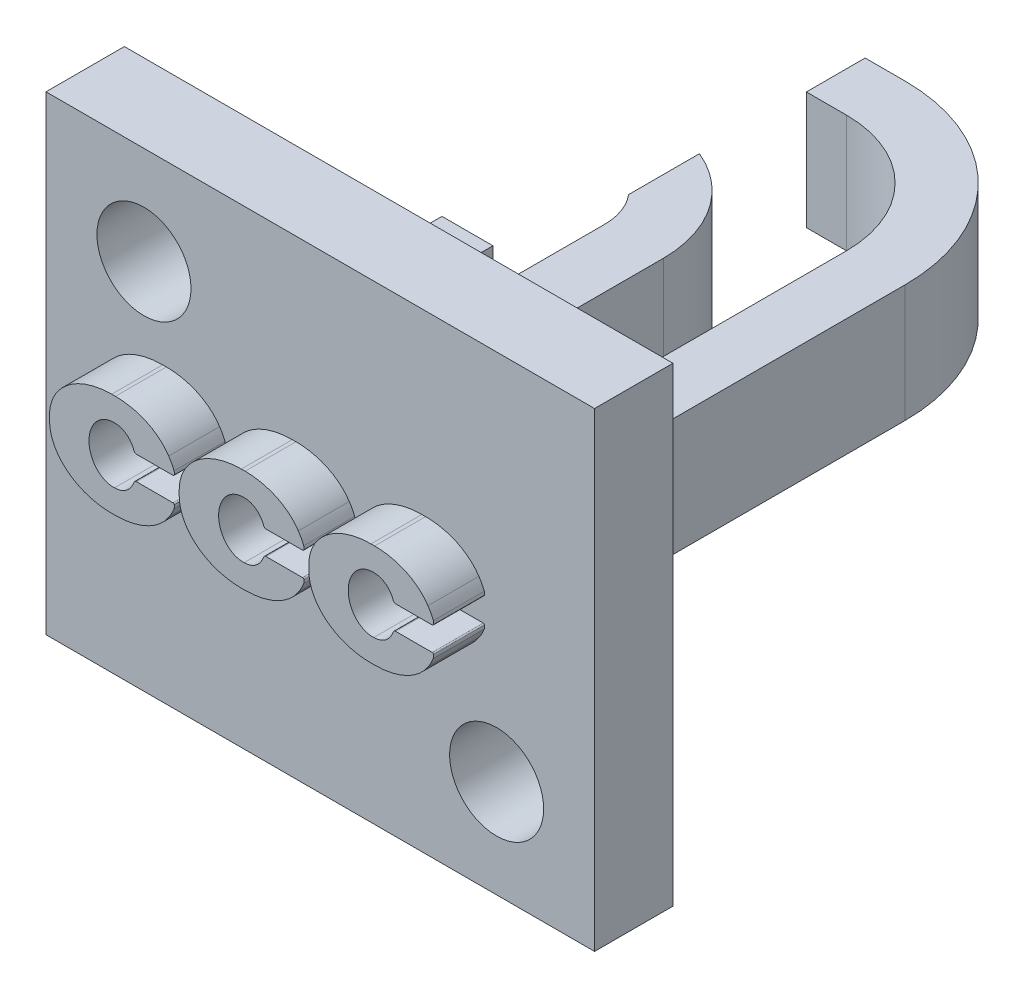
SolidWorks part; units mm, degrees
ref_plane "Front Plane" through (0, 0, 0) normal (0, 0, 1) x (1, 0, 0)
ref_plane "Top Plane" through (0, 0, 0) normal (0, 1, 0) x (1, 0, 0)
ref_plane "Right Plane" through (0, 0, 0) normal (1, 0, 0) x (0, 0, -1)
sketch "Sketch1" plane through (0, 0, 0) normal (0, 0, 1) x (1, 0, 0)
  line L1 (-7.5, 6) -> (7.5, 6)
  line L2 (-7.5, 6) -> (-7.5, -6)
  line L3 (-7.5, -6) -> (7.5, -6)
  line L4 (7.5, 6) -> (7.5, -6)
  line L5 (-7.5, 6) -> (7.5, -6) construction
  line L6 (-7.5, -6) -> (7.5, 6) construction
  point P0 (0, 0)
  dimension "D1" = 15
  dimension "D2" = 12
extrude "Boss-Extrude1" add sketch "Sketch1" along normal blind 2
sketch "Sketch2" plane through (0, 0, 2) normal (0, 0, 1) x (1, 0, 0)
  line L0 (-0.5835, 0.4438) -> (0.3524, 0.4438)
  line L1 (-1.1209, 1.4546) -> (-1.2145, 1.4546)
  line L2 (-2.8001, 0.2034) -> (-2.8001, 0.0733)
  line L3 (-1.2145, -1.1779) -> (-1.1209, -1.1779)
  line L4 (0.3478, -0.1633) -> (-0.5835, -0.1633)
  line L5 (-3.8918, 0.4438) -> (-2.956, 0.4438)
  line L6 (-4.4292, 1.4546) -> (-4.5228, 1.4546)
  line L7 (-6.1084, 0.2034) -> (-6.1084, 0.0733)
  line L8 (-4.5228, -1.1779) -> (-4.4292, -1.1779)
  line L9 (-2.9605, -0.1633) -> (-3.8918, -0.1633)
  line L10 (2.7248, 0.4438) -> (3.6607, 0.4438)
  line L11 (2.1874, 1.4546) -> (2.0938, 1.4546)
  line L12 (0.5082, 0.2034) -> (0.5082, 0.0733)
  line L13 (2.0938, -1.1779) -> (2.1874, -1.1779)
  line L14 (3.6561, -0.1633) -> (2.7248, -0.1633)
  arc A0 (-0.6452, 0.4874) -> (-0.5835, 0.4438) centre (-0.5835, 0.5092) ccw
  arc A1 (0.3524, 0.4438) -> (0.3816, 0.4686) centre (0.3479, 0.4787) ccw
  arc A2 (0.3816, 0.4686) -> (0.3774, 0.5561) centre (0.201, 0.5038) ccw
  arc A3 (0.3774, 0.5561) -> (0.2402, 0.8134) centre (-0.7046, 0.1445) ccw
  arc A4 (0.2402, -0.5368) -> (0.3727, -0.2904) centre (-0.6952, 0.1249) ccw
  arc A5 (0.3727, -0.2904) -> (0.3825, -0.1925) centre (0.2012, -0.2237) ccw
  arc A6 (0.3825, -0.1925) -> (0.3478, -0.1633) centre (0.3478, -0.1984) ccw
  arc A7 (-0.5835, -0.1633) -> (-0.6452, -0.2069) centre (-0.5835, -0.2287) ccw
  arc A8 (-3.9535, 0.4874) -> (-3.8918, 0.4438) centre (-3.8918, 0.5092) ccw
  arc A9 (-2.956, 0.4438) -> (-2.9267, 0.4686) centre (-2.9604, 0.4787) ccw
  arc A10 (-2.9267, 0.4686) -> (-2.9309, 0.5561) centre (-3.1073, 0.5038) ccw
  arc A11 (-2.9309, 0.5561) -> (-3.0681, 0.8134) centre (-4.0129, 0.1445) ccw
  arc A12 (-3.0681, -0.5368) -> (-2.9356, -0.2904) centre (-4.0035, 0.1249) ccw
  arc A13 (-2.9356, -0.2904) -> (-2.9258, -0.1925) centre (-3.1071, -0.2237) ccw
  arc A14 (-2.9258, -0.1925) -> (-2.9605, -0.1633) centre (-2.9605, -0.1984) ccw
  arc A15 (-3.8918, -0.1633) -> (-3.9535, -0.2069) centre (-3.8918, -0.2287) ccw
  arc A16 (2.6631, 0.4874) -> (2.7248, 0.4438) centre (2.7248, 0.5092) ccw
  arc A17 (3.6607, 0.4438) -> (3.6899, 0.4686) centre (3.6562, 0.4787) ccw
  arc A18 (3.6899, 0.4686) -> (3.6857, 0.5561) centre (3.5093, 0.5038) ccw
  arc A19 (3.6857, 0.5561) -> (3.5485, 0.8134) centre (2.6037, 0.1445) ccw
  arc A20 (3.5485, -0.5368) -> (3.681, -0.2904) centre (2.6131, 0.1249) ccw
  arc A21 (3.681, -0.2904) -> (3.6908, -0.1925) centre (3.5095, -0.2237) ccw
  arc A22 (3.6908, -0.1925) -> (3.6561, -0.1633) centre (3.6561, -0.1984) ccw
  arc A23 (2.7248, -0.1633) -> (2.6631, -0.2069) centre (2.7248, -0.2287) ccw
  ellipse E0 centre (-1.1734, 0.1385) end of major axis (-1.177, 0.8556) minor radius 0.6209 (-1.2015, 0.8549) -> (-1.1417, -0.5777) ccw
  ellipse E1 centre (-1.2295, 0.1385) end of major axis (-1.5121, -0.5431) minor radius 0.6039 (-0.6452, 0.4874) -> (-1.2015, 0.8549) ccw
  ellipse E2 centre (-1.2429, 0.1529) end of major axis (-2.8857, -0.0922) minor radius 1.2925 (0.2402, 0.8134) -> (-1.1209, 1.4546) ccw
  ellipse E3 centre (-1.1521, 0.1542) end of major axis (0.4928, 0.0248) minor radius 1.2979 (-1.2145, 1.4546) -> (-2.8001, 0.2034) ccw
  ellipse E4 centre (-1.1521, 0.1225) end of major axis (0.4928, 0.2518) minor radius 1.2979 (-2.8001, 0.0733) -> (-1.2145, -1.1779) ccw
  ellipse E5 centre (-1.2429, 0.1238) end of major axis (-2.8857, 0.3689) minor radius 1.2925 (-1.1209, -1.1779) -> (0.2402, -0.5368) ccw
  ellipse E6 centre (-1.2295, 0.1421) end of major axis (-0.9469, -0.5396) minor radius 0.6039 (-1.1417, -0.5777) -> (-0.6452, -0.2069) ccw
  ellipse E7 centre (-4.5378, 0.1385) end of major axis (-4.8204, -0.5431) minor radius 0.6039 (-3.9535, 0.4874) -> (-4.5098, 0.8549) ccw
  ellipse E8 centre (-4.5512, 0.1529) end of major axis (-6.194, -0.0922) minor radius 1.2925 (-3.0681, 0.8134) -> (-4.4292, 1.4546) ccw
  ellipse E9 centre (-4.4604, 0.1542) end of major axis (-6.1053, 0.2835) minor radius 1.2979 (-4.5228, 1.4546) -> (-6.1084, 0.2034) ccw
  ellipse E10 centre (-4.4604, 0.1225) end of major axis (-6.1053, -0.0069) minor radius 1.2979 (-6.1084, 0.0733) -> (-4.5228, -1.1779) ccw
  ellipse E11 centre (-4.5512, 0.1238) end of major axis (-6.194, 0.3689) minor radius 1.2925 (-4.4292, -1.1779) -> (-3.0681, -0.5368) ccw
  ellipse E12 centre (-4.5378, 0.1421) end of major axis (-4.2552, -0.5396) minor radius 0.6039 (-4.45, -0.5777) -> (-3.9535, -0.2069) ccw
  ellipse E13 centre (-4.4817, 0.1385) end of major axis (-4.4853, 0.8556) minor radius 0.6209 (-4.5098, 0.8549) -> (-4.45, -0.5777) ccw
  ellipse E14 centre (2.1349, 0.1385) end of major axis (2.1385, -0.5786) minor radius 0.6209 (2.1069, 0.8549) -> (2.1666, -0.5777) ccw
  ellipse E15 centre (2.0788, 0.1385) end of major axis (2.3614, 0.8201) minor radius 0.6039 (2.6631, 0.4874) -> (2.1069, 0.8549) ccw
  ellipse E16 centre (2.0654, 0.1529) end of major axis (3.7082, 0.3981) minor radius 1.2925 (3.5485, 0.8134) -> (2.1874, 1.4546) ccw
  ellipse E17 centre (2.1562, 0.1542) end of major axis (0.5113, 0.2835) minor radius 1.2979 (2.0938, 1.4546) -> (0.5082, 0.2034) ccw
  ellipse E18 centre (2.1562, 0.1225) end of major axis (3.8011, 0.2518) minor radius 1.2979 (0.5082, 0.0733) -> (2.0938, -1.1779) ccw
  ellipse E19 centre (2.0654, 0.1238) end of major axis (0.4226, 0.3689) minor radius 1.2925 (2.1874, -1.1779) -> (3.5485, -0.5368) ccw
  ellipse E20 centre (2.0788, 0.1421) end of major axis (2.3614, -0.5396) minor radius 0.6039 (2.1666, -0.5777) -> (2.6631, -0.2069) ccw
extrude "Boss-Extrude2" add sketch "Sketch2" along normal blind 2
sketch "Sketch3" plane through (0, 0, 0) normal (0, 1, 0) x (1, 0, 0)
  line L0 (7.5, 0) -> (-7.5, 0) construction
  line L1 (1.7287, 0) -> (3.2287, 0)
  line L2 (1.7287, 0) -> (1.7287, 12.2)
  line L3 (-3.644, -2) -> (-3.644, 5.3789) construction
  line L4 (3.2287, 0) -> (3.2287, 13.7)
  line L5 (-4.394, 0) -> (-2.894, 0)
  line L6 (-4.394, 0) -> (-4.394, 4.8)
  line L7 (-1.1926, -2) -> (-1.1926, 4.6797) construction
  line L8 (-2.894, 0) -> (-2.894, 4.8)
  line L9 (-2.894, 4.8) -> (-4.394, 4.8)
  line L10 (-1.9426, 0) -> (-0.4426, 0)
  line L13 (-1.9426, 0) -> (-1.9426, 8.2)
  line L14 (2.4787, -2) -> (2.4787, 2.787) construction
  line L15 (-0.4426, 0) -> (-0.4426, 9.7)
  line L16 (-0.4426, 9.7) -> (-3.4426, 9.7)
  line L17 (-3.4426, 13.7) -> (3.2287, 13.7)
  line L18 (-1.9426, 8.2) -> (-3.4426, 8.2)
  line L19 (-3.4426, 9.7) -> (-3.4426, 8.2)
  line L20 (-3.4426, 13.7) -> (-3.4426, 12.2)
  line L21 (-3.4426, 12.2) -> (1.7287, 12.2)
  dimension "D1" = 1.5
  dimension "D2" = 4.8
  dimension "D3" = 1.5
  dimension "D4" = 1.5
  dimension "D5" = 8.2
  dimension "D6" = 1.5
  dimension "D7" = 2.5
  dimension "D8" = 1.5
  dimension "D9" = 1.5
  dimension "D10" = 3.644
  dimension "D11" = 1.1926
  dimension "D12" = 2.4787
extrude "Boss-Extrude3" add sketch "Sketch3" along normal mid plane 3
fillet "Fillet3" radius 1.5 1 edges at (-1.9426, 0, -8.2)
fillet "Fillet4" radius 3 1 edges at (-0.4426, 0, -9.7)
fillet "Fillet5" radius 3 1 edges at (1.7287, 0, -12.2)
fillet "Fillet6" radius 4.5 1 edges at (3.2287, 0, -13.7)
sketch "Sketch4" plane through (7.5, 0, 0) normal (1, 0, 0) x (0, 0, -1)
  line L4 (0, -6) -> (0, 6)
  line L5 (0, 6) -> (-2, 6)
  line L6 (-2, 6) -> (-2, -6)
  line L7 (-2, -6) -> (0, -6)
  line L8 (0, -6) -> (0, 6)
  line L9 (0, 6) -> (-2, 6)
  line L10 (-2, 6) -> (-2, -6)
  line L11 (-2, -6) -> (0, -6)
  dimension "D1" = 0
extrude "Cut-Extrude1" cut sketch "Sketch4" against normal blind 1
sketch "Sketch5" plane through (0, 0, 0) normal (0, 0, -1) x (-1, 0, 0)
  line L0 (-6.5, -6) -> (-6.5, 6) construction
  line L1 (7.5, -6) -> (-6.5, -6) construction
  line L2 (7.5, 6) -> (7.5, -6) construction
  line L3 (-6.5, 6) -> (7.5, 6) construction
  circle A0 centre (-4, -3.5) radius 1.2
  circle A1 centre (5, 3.5) radius 1.2
  dimension "D1" = 2.4
  dimension "D2" = 2.5
  dimension "D3" = 2.5
  dimension "D4" = 2.5
  dimension "D5" = 2.5
extrude "Cut-Extrude2" cut sketch "Sketch5" against normal through all
sketch "Sketch6" plane through (0, 0, 4) normal (0, 0, 1) x (1, 0, 0)
  line L0 (2.7248, 0.4438) -> (3.6607, 0.4438) construction
  line L1 (2.1874, 1.4546) -> (2.0938, 1.4546) construction
  line L2 (0.5082, 0.2034) -> (0.5082, 0.0733) construction
  line L3 (2.0938, -1.1779) -> (2.1874, -1.1779) construction
  line L4 (3.6561, -0.1633) -> (2.7248, -0.1633) construction
  line L5 (-0.5835, 0.4438) -> (0.3524, 0.4438) construction
  line L6 (-1.1209, 1.4546) -> (-1.2145, 1.4546) construction
  line L7 (-2.8001, 0.2034) -> (-2.8001, 0.0733) construction
  line L8 (-1.2145, -1.1779) -> (-1.1209, -1.1779) construction
  line L9 (0.3478, -0.1633) -> (-0.5835, -0.1633) construction
  line L10 (-3.8918, 0.4438) -> (-2.956, 0.4438) construction
  line L11 (-4.4292, 1.4546) -> (-4.5228, 1.4546) construction
  line L12 (-6.1084, 0.2034) -> (-6.1084, 0.0733) construction
  line L13 (-4.5228, -1.1779) -> (-4.4292, -1.1779) construction
  line L14 (-2.9605, -0.1633) -> (-3.8918, -0.1633) construction
  line L15 (2.7248, 0.4438) -> (3.6607, 0.4438)
  line L16 (2.1874, 1.4546) -> (2.0938, 1.4546)
  line L17 (0.5082, 0.2034) -> (0.5082, 0.0733)
  line L18 (2.0938, -1.1779) -> (2.1874, -1.1779)
  line L19 (3.6561, -0.1633) -> (2.7248, -0.1633)
  line L20 (-0.5835, 0.4438) -> (0.3524, 0.4438)
  line L21 (-1.1209, 1.4546) -> (-1.2145, 1.4546)
  line L22 (-2.8001, 0.2034) -> (-2.8001, 0.0733)
  line L23 (-1.2145, -1.1779) -> (-1.1209, -1.1779)
  line L24 (0.3478, -0.1633) -> (-0.5835, -0.1633)
  line L25 (-3.8918, 0.4438) -> (-2.956, 0.4438)
  line L26 (-4.4292, 1.4546) -> (-4.5228, 1.4546)
  line L27 (-6.1084, 0.2034) -> (-6.1084, 0.0733)
  line L28 (-4.5228, -1.1779) -> (-4.4292, -1.1779)
  line L29 (-2.9605, -0.1633) -> (-3.8918, -0.1633)
  arc A0 (2.6631, 0.4874) -> (2.7248, 0.4438) centre (2.7248, 0.5092) ccw construction
  arc A1 (3.6607, 0.4438) -> (3.6899, 0.4686) centre (3.6562, 0.4787) ccw construction
  arc A2 (3.6899, 0.4686) -> (3.6857, 0.5561) centre (3.5093, 0.5038) ccw construction
  arc A3 (3.6857, 0.5561) -> (3.5485, 0.8134) centre (2.6037, 0.1445) ccw construction
  arc A4 (3.5485, -0.5368) -> (3.681, -0.2904) centre (2.6131, 0.1249) ccw construction
  arc A5 (3.681, -0.2904) -> (3.6908, -0.1925) centre (3.5095, -0.2237) ccw construction
  arc A6 (3.6908, -0.1925) -> (3.6561, -0.1633) centre (3.6561, -0.1984) ccw construction
  arc A7 (2.7248, -0.1633) -> (2.6631, -0.2069) centre (2.7248, -0.2287) ccw construction
  arc A8 (-0.6452, 0.4874) -> (-0.5835, 0.4438) centre (-0.5835, 0.5092) ccw construction
  arc A9 (0.3524, 0.4438) -> (0.3816, 0.4686) centre (0.3479, 0.4787) ccw construction
  arc A10 (0.3816, 0.4686) -> (0.3774, 0.5561) centre (0.201, 0.5038) ccw construction
  arc A11 (0.3774, 0.5561) -> (0.2402, 0.8134) centre (-0.7046, 0.1445) ccw construction
  arc A12 (0.2402, -0.5368) -> (0.3727, -0.2904) centre (-0.6952, 0.1249) ccw construction
  arc A13 (0.3727, -0.2904) -> (0.3825, -0.1925) centre (0.2012, -0.2237) ccw construction
  arc A14 (0.3825, -0.1925) -> (0.3478, -0.1633) centre (0.3478, -0.1984) ccw construction
  arc A15 (-0.5835, -0.1633) -> (-0.6452, -0.2069) centre (-0.5835, -0.2287) ccw construction
  arc A16 (-3.9535, 0.4874) -> (-3.8918, 0.4438) centre (-3.8918, 0.5092) ccw construction
  arc A17 (-2.956, 0.4438) -> (-2.9267, 0.4686) centre (-2.9604, 0.4787) ccw construction
  arc A18 (-2.9267, 0.4686) -> (-2.9309, 0.5561) centre (-3.1073, 0.5038) ccw construction
  arc A19 (-2.9309, 0.5561) -> (-3.0681, 0.8134) centre (-4.0129, 0.1445) ccw construction
  arc A20 (-3.0681, -0.5368) -> (-2.9356, -0.2904) centre (-4.0035, 0.1249) ccw construction
  arc A21 (-2.9356, -0.2904) -> (-2.9258, -0.1925) centre (-3.1071, -0.2237) ccw construction
  arc A22 (-2.9258, -0.1925) -> (-2.9605, -0.1633) centre (-2.9605, -0.1984) ccw construction
  arc A23 (-3.8918, -0.1633) -> (-3.9535, -0.2069) centre (-3.8918, -0.2287) ccw construction
  arc A24 (2.6631, 0.4874) -> (2.7248, 0.4438) centre (2.7248, 0.5092) ccw
  arc A25 (3.6607, 0.4438) -> (3.6899, 0.4686) centre (3.6562, 0.4787) ccw
  arc A26 (3.6899, 0.4686) -> (3.6857, 0.5561) centre (3.5093, 0.5038) ccw
  arc A27 (3.6857, 0.5561) -> (3.5485, 0.8134) centre (2.6037, 0.1445) ccw
  arc A28 (3.5485, -0.5368) -> (3.681, -0.2904) centre (2.6131, 0.1249) ccw
  arc A29 (3.681, -0.2904) -> (3.6908, -0.1925) centre (3.5095, -0.2237) ccw
  arc A30 (3.6908, -0.1925) -> (3.6561, -0.1633) centre (3.6561, -0.1984) ccw
  arc A31 (2.7248, -0.1633) -> (2.6631, -0.2069) centre (2.7248, -0.2287) ccw
  arc A32 (-0.6452, 0.4874) -> (-0.5835, 0.4438) centre (-0.5835, 0.5092) ccw
  arc A33 (0.3524, 0.4438) -> (0.3816, 0.4686) centre (0.3479, 0.4787) ccw
  arc A34 (0.3816, 0.4686) -> (0.3774, 0.5561) centre (0.201, 0.5038) ccw
  arc A35 (0.3774, 0.5561) -> (0.2402, 0.8134) centre (-0.7046, 0.1445) ccw
  arc A36 (0.2402, -0.5368) -> (0.3727, -0.2904) centre (-0.6952, 0.1249) ccw
  arc A37 (0.3727, -0.2904) -> (0.3825, -0.1925) centre (0.2012, -0.2237) ccw
  arc A38 (0.3825, -0.1925) -> (0.3478, -0.1633) centre (0.3478, -0.1984) ccw
  arc A39 (-0.5835, -0.1633) -> (-0.6452, -0.2069) centre (-0.5835, -0.2287) ccw
  arc A40 (-3.9535, 0.4874) -> (-3.8918, 0.4438) centre (-3.8918, 0.5092) ccw
  arc A41 (-2.956, 0.4438) -> (-2.9267, 0.4686) centre (-2.9604, 0.4787) ccw
  arc A42 (-2.9267, 0.4686) -> (-2.9309, 0.5561) centre (-3.1073, 0.5038) ccw
  arc A43 (-2.9309, 0.5561) -> (-3.0681, 0.8134) centre (-4.0129, 0.1445) ccw
  arc A44 (-3.0681, -0.5368) -> (-2.9356, -0.2904) centre (-4.0035, 0.1249) ccw
  arc A45 (-2.9356, -0.2904) -> (-2.9258, -0.1925) centre (-3.1071, -0.2237) ccw
  arc A46 (-2.9258, -0.1925) -> (-2.9605, -0.1633) centre (-2.9605, -0.1984) ccw
  arc A47 (-3.8918, -0.1633) -> (-3.9535, -0.2069) centre (-3.8918, -0.2287) ccw
  ellipse E0 centre (2.0788, 0.1385) end of major axis (1.7962, -0.5431) minor radius 0.6039 (2.6631, 0.4874) -> (2.1069, 0.8549) ccw construction
  ellipse E1 centre (2.0654, 0.1529) end of major axis (0.4226, -0.0922) minor radius 1.2925 (3.5485, 0.8134) -> (2.1874, 1.4546) ccw construction
  ellipse E2 centre (2.1562, 0.1542) end of major axis (0.5113, 0.2835) minor radius 1.2979 (2.0938, 1.4546) -> (0.5082, 0.2034) ccw construction
  ellipse E3 centre (2.1562, 0.1225) end of major axis (3.8011, 0.2518) minor radius 1.2979 (0.5082, 0.0733) -> (2.0938, -1.1779) ccw construction
  ellipse E4 centre (2.0654, 0.1238) end of major axis (0.4226, 0.3689) minor radius 1.2925 (2.1874, -1.1779) -> (3.5485, -0.5368) ccw construction
  ellipse E5 centre (2.0788, 0.1421) end of major axis (2.3614, -0.5396) minor radius 0.6039 (2.1666, -0.5777) -> (2.6631, -0.2069) ccw construction
  ellipse E6 centre (2.1349, 0.1385) end of major axis (2.1385, -0.5786) minor radius 0.6209 (2.1069, 0.8549) -> (2.1666, -0.5777) ccw construction
  ellipse E7 centre (-1.2295, 0.1385) end of major axis (-1.5121, -0.5431) minor radius 0.6039 (-0.6452, 0.4874) -> (-1.2015, 0.8549) ccw construction
  ellipse E8 centre (-1.2429, 0.1529) end of major axis (0.3999, 0.3981) minor radius 1.2925 (0.2402, 0.8134) -> (-1.1209, 1.4546) ccw construction
  ellipse E9 centre (-1.1521, 0.1542) end of major axis (-2.797, 0.2835) minor radius 1.2979 (-1.2145, 1.4546) -> (-2.8001, 0.2034) ccw construction
  ellipse E10 centre (-1.1521, 0.1225) end of major axis (0.4928, 0.2518) minor radius 1.2979 (-2.8001, 0.0733) -> (-1.2145, -1.1779) ccw construction
  ellipse E11 centre (-1.2429, 0.1238) end of major axis (0.3999, -0.1214) minor radius 1.2925 (-1.1209, -1.1779) -> (0.2402, -0.5368) ccw construction
  ellipse E12 centre (-1.2295, 0.1421) end of major axis (-0.9469, -0.5396) minor radius 0.6039 (-1.1417, -0.5777) -> (-0.6452, -0.2069) ccw construction
  ellipse E13 centre (-1.1734, 0.1385) end of major axis (-1.1698, -0.5786) minor radius 0.6209 (-1.2015, 0.8549) -> (-1.1417, -0.5777) ccw construction
  ellipse E14 centre (-4.5378, 0.1385) end of major axis (-4.8204, -0.5431) minor radius 0.6039 (-3.9535, 0.4874) -> (-4.5098, 0.8549) ccw construction
  ellipse E15 centre (-4.5512, 0.1529) end of major axis (-2.9084, 0.3981) minor radius 1.2925 (-3.0681, 0.8134) -> (-4.4292, 1.4546) ccw construction
  ellipse E16 centre (-4.4604, 0.1542) end of major axis (-6.1053, 0.2835) minor radius 1.2979 (-4.5228, 1.4546) -> (-6.1084, 0.2034) ccw construction
  ellipse E17 centre (-4.4604, 0.1225) end of major axis (-2.8155, 0.2518) minor radius 1.2979 (-6.1084, 0.0733) -> (-4.5228, -1.1779) ccw construction
  ellipse E18 centre (-4.5512, 0.1238) end of major axis (-6.194, 0.3689) minor radius 1.2925 (-4.4292, -1.1779) -> (-3.0681, -0.5368) ccw construction
  ellipse E19 centre (-4.5378, 0.1421) end of major axis (-4.2552, -0.5396) minor radius 0.6039 (-4.45, -0.5777) -> (-3.9535, -0.2069) ccw construction
  ellipse E20 centre (-4.4817, 0.1385) end of major axis (-4.4781, -0.5786) minor radius 0.6209 (-4.5098, 0.8549) -> (-4.45, -0.5777) ccw construction
  ellipse E21 centre (2.0788, 0.1385) end of major axis (1.7962, -0.5431) minor radius 0.6039 (2.6631, 0.4874) -> (2.1069, 0.8549) ccw
  ellipse E22 centre (2.0654, 0.1529) end of major axis (3.7082, 0.3981) minor radius 1.2925 (3.5485, 0.8134) -> (2.1874, 1.4546) ccw
  ellipse E23 centre (2.1562, 0.1542) end of major axis (0.5113, 0.2835) minor radius 1.2979 (2.0938, 1.4546) -> (0.5082, 0.2034) ccw
  ellipse E24 centre (2.1562, 0.1225) end of major axis (3.8011, 0.2518) minor radius 1.2979 (0.5082, 0.0733) -> (2.0938, -1.1779) ccw
  ellipse E25 centre (2.0654, 0.1238) end of major axis (0.4226, 0.3689) minor radius 1.2925 (2.1874, -1.1779) -> (3.5485, -0.5368) ccw
  ellipse E26 centre (2.0788, 0.1421) end of major axis (2.3614, -0.5396) minor radius 0.6039 (2.1666, -0.5777) -> (2.6631, -0.2069) ccw
  ellipse E27 centre (2.1349, 0.1385) end of major axis (2.1385, -0.5786) minor radius 0.6209 (2.1069, 0.8549) -> (2.1666, -0.5777) ccw
  ellipse E28 centre (-1.2295, 0.1385) end of major axis (-1.5121, -0.5431) minor radius 0.6039 (-0.6452, 0.4874) -> (-1.2015, 0.8549) ccw
  ellipse E29 centre (-1.2429, 0.1529) end of major axis (0.3999, 0.3981) minor radius 1.2925 (0.2402, 0.8134) -> (-1.1209, 1.4546) ccw
  ellipse E30 centre (-1.1521, 0.1542) end of major axis (-2.797, 0.2835) minor radius 1.2979 (-1.2145, 1.4546) -> (-2.8001, 0.2034) ccw
  ellipse E31 centre (-1.1521, 0.1225) end of major axis (0.4928, 0.2518) minor radius 1.2979 (-2.8001, 0.0733) -> (-1.2145, -1.1779) ccw
  ellipse E32 centre (-1.2429, 0.1238) end of major axis (-2.8857, 0.3689) minor radius 1.2925 (-1.1209, -1.1779) -> (0.2402, -0.5368) ccw
  ellipse E33 centre (-1.2295, 0.1421) end of major axis (-0.9469, -0.5396) minor radius 0.6039 (-1.1417, -0.5777) -> (-0.6452, -0.2069) ccw
  ellipse E34 centre (-1.1734, 0.1385) end of major axis (-1.1698, -0.5786) minor radius 0.6209 (-1.2015, 0.8549) -> (-1.1417, -0.5777) ccw
  ellipse E35 centre (-4.5378, 0.1385) end of major axis (-4.8204, -0.5431) minor radius 0.6039 (-3.9535, 0.4874) -> (-4.5098, 0.8549) ccw
  ellipse E36 centre (-4.5512, 0.1529) end of major axis (-2.9084, 0.3981) minor radius 1.2925 (-3.0681, 0.8134) -> (-4.4292, 1.4546) ccw
  ellipse E37 centre (-4.4604, 0.1542) end of major axis (-6.1053, 0.2835) minor radius 1.2979 (-4.5228, 1.4546) -> (-6.1084, 0.2034) ccw
  ellipse E38 centre (-4.4604, 0.1225) end of major axis (-2.8155, 0.2518) minor radius 1.2979 (-6.1084, 0.0733) -> (-4.5228, -1.1779) ccw
  ellipse E39 centre (-4.5512, 0.1238) end of major axis (-6.194, 0.3689) minor radius 1.2925 (-4.4292, -1.1779) -> (-3.0681, -0.5368) ccw
  ellipse E40 centre (-4.5378, 0.1421) end of major axis (-4.2552, -0.5396) minor radius 0.6039 (-4.45, -0.5777) -> (-3.9535, -0.2069) ccw
  ellipse E41 centre (-4.4817, 0.1385) end of major axis (-4.4781, -0.5786) minor radius 0.6209 (-4.5098, 0.8549) -> (-4.45, -0.5777) ccw
extrude "Cut-Extrude3" cut sketch "Sketch6" against normal blind 0.7
sketch "Sketch7" plane through (0, 1.5, 0) normal (0, 1, 0) x (1, 0, 0)
  line L0 (-1.2713, 13.7) -> (-3.4426, 13.7) construction
  line L1 (-3.4426, 13.7) -> (-2.294, 13.7)
  line L2 (-3.4426, 13.7) -> (-3.4426, 7.5)
  line L3 (-3.4426, 7.5) -> (-2.294, 7.5)
  line L4 (-2.294, 13.7) -> (-2.294, 7.5)
  line L5 (-2.594, 7.5) -> (-2.594, 10.2) construction
  line L6 (-3.4426, 13.7) -> (-3.4426, 12.2) construction
  dimension "D1" = 0.3
extrude "Cut-Extrude4" cut sketch "Sketch7" against normal through all
sketch "Sketch8" plane through (0, 1.5, 0) normal (0, 1, 0) x (1, 0, 0)
  line L0 (6.5, 0) -> (-7.5, 0) construction
  line L1 (-4.394, 4.8) -> (-4.194, 4.8)
  line L2 (-4.394, 4.8) -> (-4.394, 0)
  line L3 (-4.394, 0) -> (-4.194, 0)
  line L4 (-4.194, 4.8) -> (-4.194, 0)
  dimension "D1" = 0.2
extrude "Cut-Extrude5" cut sketch "Sketch8" against normal through all
